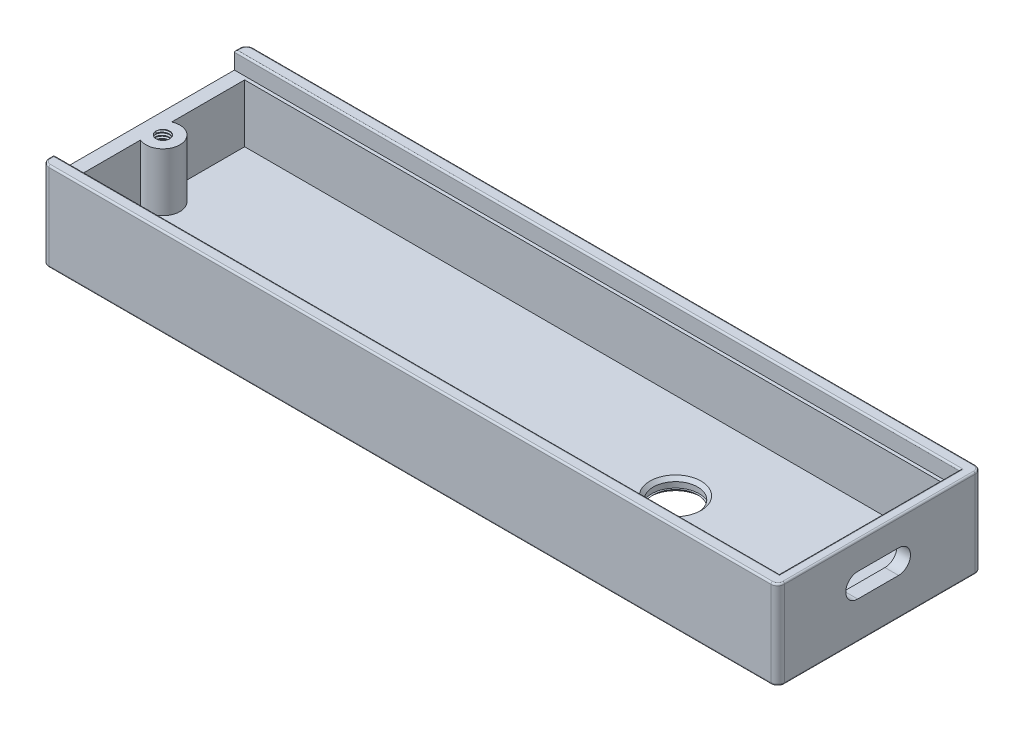
SolidWorks part; units mm, degrees
material "ABS"
ref_plane "Front Plane" through (0, 0, 0) normal (0, 0, 1) x (1, 0, 0)
ref_plane "Top Plane" through (0, 0, 0) normal (0, 1, 0) x (1, 0, 0)
ref_plane "Right Plane" through (0, 0, 0) normal (1, 0, 0) x (0, 0, -1)
sketch "Sketch1" plane through (0, 0, 0) normal (0, 1, 0) x (1, 0, 0)
  line L1 (0, 0) -> (108, 0)
  line L2 (0, 0) -> (0, -30)
  line L3 (0, -30) -> (108, -30)
  line L4 (108, 0) -> (108, -30)
  dimension "D1" = 108
  dimension "D2" = 30
extrude "Boss-Extrude1" add sketch "Sketch1" against normal blind 13
sketch "Sketch2" plane through (0, 0, 0) normal (0, 1, 0) x (1, 0, 0)
  line L0 (0, -30) -> (108, -30) construction
  line L1 (0, -1.75) -> (106.5, -1.75)
  line L2 (0, -1.75) -> (0, -28.25)
  line L3 (0, -28.25) -> (106.5, -28.25)
  line L4 (106.5, -1.75) -> (106.5, -28.25)
  line L6 (108, -30) -> (108, 0) construction
  line L8 (0, 0) -> (0, -30) construction
  line L10 (108, 0) -> (0, 0) construction
  dimension "D1" = 1.75
  dimension "D2" = 1.75
  dimension "D3" = 1.5
extrude "Cut-Extrude1" cut sketch "Sketch2" against normal blind 2.5
sketch "Sketch3" plane through (0, 0, 0) normal (0, 1, 0) x (1, 0, 0)
  line L0 (106.5, -1.75) -> (0, -1.75) construction
  line L1 (2, -2.25) -> (106, -2.25)
  line L2 (2, -2.25) -> (2, -27.75)
  line L3 (2, -27.75) -> (106, -27.75)
  line L4 (106, -2.25) -> (106, -27.75)
  line L5 (106.5, -28.25) -> (106.5, -1.75) construction
  line L6 (0, -28.25) -> (106.5, -28.25) construction
  line L7 (0, -1.75) -> (0, -28.25) construction
  dimension "D1" = 0.5
  dimension "D2" = 0.5
  dimension "D3" = 0.5
  dimension "D4" = 2
extrude "Cut-Extrude2" cut sketch "Sketch3" against normal blind 11
fillet "Fillet1" radius 0.25 12 edges at (0, 0, 0.875) (54, 0, 0) (108, 0, 15) (54, 0, 30) (0, 0, 29.125) (53.25, 0, 28.25) (106.5, 0, 15) (53.25, 0, 1.75) (54, -13, 30) (108, -13, 15) (54, -13, 0) (0, -13, 15)
fillet "Fillet2" radius 1 12 edges at (107.9268, -0.0732, 29.9268) (107.9268, -0.0732, 0.0732) (0.0732, -0.0732, 0.0732) (0.0732, -0.0732, 29.9268) (0, -6.5, 30) (0, -6.5, 0) (108, -6.5, 0) (108, -6.5, 30) (107.9268, -12.9268, 29.9268) (107.9268, -12.9268, 0.0732) (0.0732, -12.9268, 0.0732) (0.0732, -12.9268, 29.9268)
sketch "Sketch4" plane through (0, -11, 0) normal (0, 1, 0) x (1, 0, 0)
  line L0 (0, -1.75) -> (0, -28.25) construction
  line L2 (0, -28.25) -> (106.5, -28.25) construction
  circle A0 centre (3, -15.25) radius 2.5
  dimension "D1" = 5
  dimension "D2" = 3
  dimension "D3" = 13
extrude "Boss-Extrude2" add sketch "Sketch4" along normal up to surface (8.5 mm away) up to face at (54, -2.5, 15)
hole_wizard "Ø2.0 (2) Diameter Hole1" positions "3DSketch1" profile "Sketch5" hole size "Ø2.0" standard "ISO"
sketch3d "3DSketch1"
  line L0 (0, -2.5, 1.75) -> (0, -2.5, 28.25) construction
  point P0 (3, -2.5, 15.25)
  dimension "D1" = 3
  dimension "D2" = 13.5
sketch "Sketch5" plane through (3, -2.5, 15.25) normal (1, 0, 0) x (0, 0, 1)
  line L0 (0, 0) -> (0, 5.6009)
  line L1 (0, 5.6009) -> (1, 5)
  line L2 (1, 5) -> (1, 0)
  line L5 (1, 0) -> (0, 0)
  line L10 (0, 5.6009) -> (-1, 5) construction
  line L11 (0, -6.35) -> (0, 107.95) construction
  dimension "Hole Dia." = 2
  dimension "Hole Depth" = 5
  dimension "Drill Angle" = 118
thread "Thread1" pitch 0.4 method cut profile "Thread Profile1" start angle 0, offset 0, length 4, pitch 0.4, diameter 2
ref_plane "Plane4" through (2, -2.5, 15.25) normal (0, 0, 1) x (-1, 0, 0)
sketch "Thread Profile1" plane through (2, -2.5, 15.25) normal (0, 0, 1) x (-1, 0, 0)
  line L0 (0, 0) -> (0, 0.4) construction
  line L1 (0, 0) -> (0.2165, 0.125)
  line L2 (0.2165, 0.125) -> (0.2165, 0.175)
  line L3 (0.2165, 0.175) -> (0, 0.3)
  line L4 (0.2165, 0.15) -> (0, 0.15) construction
  line L11 (0, 0) -> (0, 0.3)
  point P2 (0, 0)
  dimension "Pitch" = 0.4
  dimension "Profile_Angle" = 60
  dimension "Profile_Land" = 0.05
  dimension "Profile_Height" = 0.2165
sketch "Sketch9" plane through (108, 0, 0) normal (1, 0, 0) x (0, 0, -1)
  line L0 (-18.25, -5.75) -> (-12.25, -5.75) construction
  line L1 (-18.25, -4) -> (-12.25, -4)
  line L2 (-18.25, -7.5) -> (-12.25, -7.5)
  line L5 (-30, -12.75) -> (-30, -0.25) construction
  line L6 (-29, -12.75) -> (-1, -12.75) construction
  arc A0 (-18.25, -4) -> (-18.25, -7.5) centre (-18.25, -5.75) ccw
  arc A1 (-12.25, -7.5) -> (-12.25, -4) centre (-12.25, -5.75) ccw
  point P2 (-15.25, -5.75)
  dimension "D1" = 6
  dimension "D2" = 7
  dimension "D3" = 3.5
  dimension "D4" = 14.75
extrude "Cut-Extrude3" cut sketch "Sketch9" against normal up to next
sketch "Sketch10" plane through (0, -13, 0) normal (0, -1, 0) x (1, 0, 0)
  line L0 (107, 29.75) -> (1, 29.75) construction
  line L1 (0.25, 29) -> (0.25, 1) construction
  line L2 (0.25, 14.75) -> (107.75, 14.75) construction
  line L4 (54, 29.25) -> (54, 0) construction
  circle A0 centre (3.25, 26.75) radius 0.75
  circle A1 centre (3.25, 2.75) radius 0.75
  circle A2 centre (104.75, 2.75) radius 0.75
  circle A3 centre (104.75, 26.75) radius 0.75
  dimension "D3" = 1.5
  dimension "D1" = 3
  dimension "D2" = 3
extrude "Boss-Extrude3" add sketch "Sketch10" along normal blind 0.5
fillet "Fillet3" radius 0.25 4 edges at (3.25, -13.5, 26) (104.75, -13.5, 27.5) (104.75, -13.5, 2) (3.25, -13.5, 3.5)
sketch "Sketch11" plane through (106.5, 0, 0) normal (-1, 0, 0) x (0, 0, 1)
  line L0 (28.25, -2.5) -> (28.25, -0.25) construction
  line L1 (1.75, -2.5) -> (28.25, -2.5)
  line L2 (1.75, -2.5) -> (1.75, -1.375)
  line L3 (1.75, -1.375) -> (28.25, -1.375)
  line L4 (28.25, -2.5) -> (28.25, -1.375)
extrude "Cut-Extrude4" cut sketch "Sketch11" against normal blind 1
sketch "Sketch13" plane through (0, -11, 0) normal (0, 1, 0) x (1, 0, 0)
  line L0 (106, -27.75) -> (106, -2.25) construction
  line L2 (1, -30) -> (107, -30) construction
  circle A0 centre (78, -15) radius 3.25
  dimension "D1" = 6.5
  dimension "D2" = 28
  dimension "D3" = 15
extrude "Cut-Extrude5" cut sketch "Sketch13" against normal through all
ref_plane "Plane5" through (0, -12, 0) normal (0, 1, 0) x (1, 0, 0)
sketch "Sketch15" plane through (0, -12, 0) normal (0, 1, 0) x (1, 0, 0)
  circle A0 centre (78, -15) radius 3.5
  dimension "D1" = 7
extrude "Cut-Extrude6" cut sketch "Sketch15" against normal mid plane 1
chamfer "Chamfer3" distance 0.5 angle 45 2 edges at (78, -13, 18.25) (78, -11, 18.25)
sketch "Sketch14" plane through (108, 0, 0) normal (1, 0, 0) x (0, 0, -1)
  line L0 (-20, -1.0063) -> (-20, -7.8524)
  line L1 (-10.5, -1.7162) -> (-10.5, -8.1315)
  arc A0 (-12.25, -7.5) -> (-12.25, -4) centre (-12.25, -5.75) ccw construction
  arc A1 (-18.25, -4) -> (-18.25, -7.5) centre (-18.25, -5.75) ccw construction
